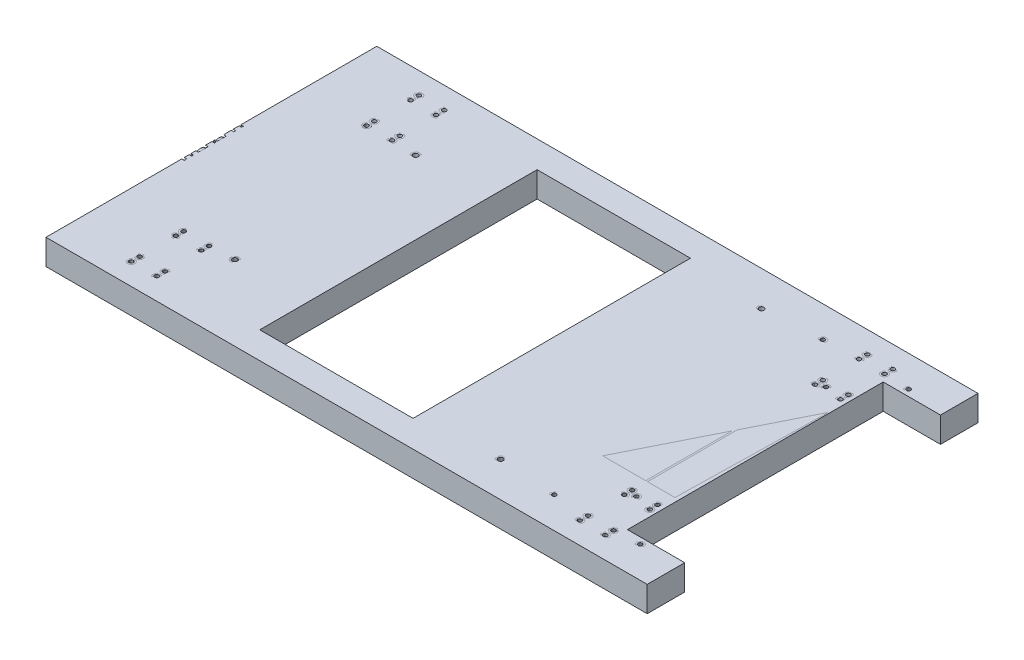
SolidWorks part; units mm, degrees
material "Magnesium Alloy"
ref_plane "Front Plane" through (0, 0, 0) normal (0, 0, 1) x (1, 0, 0)
ref_plane "Top Plane" through (0, 0, 0) normal (0, 1, 0) x (1, 0, 0)
ref_plane "Right Plane" through (0, 0, 0) normal (1, 0, 0) x (0, 0, -1)
sketch "Sketch1" plane through (0, 0, 0) normal (0, 1, 0) x (1, 0, 0)
  line L0 (0, 471.9498) -> (0, -504.9384) construction
  line L1 (-300.0375, 165.1) -> (300.0375, 165.1)
  line L2 (-300.0375, 165.1) -> (-300.0375, -165.1)
  line L3 (-300.0375, -165.1) -> (300.0375, -165.1)
  line L4 (300.0375, 165.1) -> (300.0375, -165.1)
  line L5 (-636.3607, 0) -> (748.0963, 0) construction
  dimension "D1" = 600.075
  dimension "D2" = 330.2
extrude "Boss-Extrude1" add sketch "Sketch1" along normal blind 25.4
sketch "Sketch2" plane through (-300.0375, 0, 0) normal (-1, 0, 0) x (0, 0, 1)
  line L0 (-165.1, 12.7) -> (165.1, 12.7) construction
  line L1 (-165.1, 25.4) -> (-165.1, 0) construction
  line L2 (165.1, 25.4) -> (165.1, 0) construction
  text T0 "Back" font "Century Gothic" height 19.05
extrude "Cut-Extrude1" cut sketch "Sketch2" against normal blind 2.54
sketch "Sketch3" plane through (300.0375, 0, 0) normal (1, 0, 0) x (0, 0, -1)
  line L0 (-165.1, 12.7) -> (165.1, 12.7) construction
  line L1 (-165.1, 25.4) -> (-165.1, 0) construction
  line L2 (165.1, 25.4) -> (165.1, 0) construction
  text T0 "Front" font "Century Gothic" height 19.05
extrude "Cut-Extrude2" cut sketch "Sketch3" against normal blind 2.54
sketch "Sketch4" plane through (0, 0, 0) normal (0, -1, 0) x (1, 0, 0)
  line L0 (407.1831, 0) -> (-551.8052, 0) construction
  line L1 (-113.3475, 138.43) -> (39.6875, 138.43)
  line L2 (-113.3475, 138.43) -> (-113.3475, -138.43)
  line L3 (-113.3475, -138.43) -> (39.6875, -138.43)
  line L4 (39.6875, 138.43) -> (39.6875, -138.43)
  line L5 (55, 0) -> (-55, 0) construction
  line L6 (-300.0375, -165.1) -> (-300.0375, 165.1) construction
  line L7 (300.0375, 165.1) -> (300.0375, -165.1) construction
  line L10 (-300.0375, 165.1) -> (300.0375, 165.1) construction
  dimension "D1" = 186.69
  dimension "D2" = 260.35
  dimension "D3" = 26.67
extrude "Cut-Extrude3" cut sketch "Sketch4" against normal up to next
ref_plane "Plane1" through (223.8375, 0, 0) normal (1, 0, 0) x (0, 0, -1)
ref_plane "Plane2" through (-223.8375, 0, 0) normal (-1, 0, 0) x (0, 0, 1)
sketch "Sketch7" plane through (0, 25.4, 0) normal (0, 1, 0) x (1, 0, 0)
  line L0 (-300.0375, -29.6562) -> (-300.0375, -165.1) construction
  line L1 (-300.0375, -165.1) -> (300.0375, -165.1) construction
  point P0 (-236.5375, -91.2978)
  point P1 (-236.5375, -135.2474)
  point P2 (-211.1375, -135.2474)
  point P3 (-211.1375, -91.2978)
  dimension "D1" = 63.5
  dimension "D2" = 63.5
  dimension "D3" = 88.9
  dimension "D4" = 88.9
  dimension "D5" = 29.8526
  dimension "D6" = 29.8526
  dimension "D7" = 43.9496
  dimension "D8" = 43.9496
hole_wizard "#21 (0.159) Diameter Hole1" positions "Sketch10" profile "Sketch11" hole size "#21" standard "ANSI Inch" end condition through all
sketch "Sketch10" plane through (0, 25.4, 0) normal (0, 1, 0) x (1, 0, 0)
  point P0 (-236.5375, -91.2978)
  point P3 (-211.1375, -91.2978)
  point P6 (-211.1375, -135.2474)
  point P9 (-236.5375, -135.2474)
sketch "Sketch11" plane through (-236.5375, 25.4, 91.2978) normal (1, 0, 0) x (0, 0, 1)
  line L0 (0, 0) -> (0, 25.4)
  line L1 (0, 25.4) -> (2.0193, 25.4)
  line L2 (2.0193, 25.4) -> (2.0193, 0)
  line L5 (2.0193, 0) -> (0, 0)
  line L11 (0, -6.35) -> (0, 107.95) construction
  dimension "Thru Hole Dia." = 4.0386
  dimension "Thru Hole Depth" = 25.4
mirror "Mirror3" about plane through (0, 0, 0) normal (1, 0, 0) of "#21 (0.159) Diameter Hole1"
mirror "Mirror4" about plane through (0, 0, 0) normal (0, 0, 1) of "Mirror3"
ref_axis "Axis1" through (-236.5375, 0, 91.2978) along (0, 1, 0)
ref_axis "Axis2" through (-211.1375, 0, 91.2978) along (0, 1, 0)
ref_axis "Axis3" through (-211.1375, 0, 135.2474) along (0, 1, 0)
ref_axis "Axis4" through (-236.5375, 0, 135.2474) along (0, 1, 0)
sketch "Sketch12" plane through (0, 25.4, 0) normal (0, 1, 0) x (1, 0, 0)
  point P0 (78.8458, -130.175)
ref_plane "Plane3" through (0, 0, 130.175) normal (0, 0, 1) x (1, 0, 0)
sketch "Sketch13" plane through (0, 0, 130.175) normal (0, 0, 1) x (1, 0, 0)
  line L0 (78.8458, 65.775) -> (78.8458, -43.461) construction
hole_wizard "Ø5.0mm Dowel Hole2" positions "Sketch16" profile "Sketch17" hole size "Ø5.0" standard "ANSI Metric" end condition through all
sketch "Sketch16" plane through (0, 25.4, 0) normal (0, 1, 0) x (1, 0, 0)
  circle A0 centre (118.8508, -130.175) radius 2.54
  circle A1 centre (118.8508, 130.175) radius 2.54
  circle A2 centre (-186.3725, 90.17) radius 2.54
  circle A3 centre (-186.3725, -90.17) radius 2.54
  point P3 (118.8508, -130.175)
  point P9 (118.8508, 130.175)
  point P12 (-186.3725, 90.17)
  point P21 (-186.3725, -90.17)
  point P24 (118.8508, -130.175)
sketch "Sketch17" plane through (118.8508, 25.4, 130.175) normal (1, 0, 0) x (0, 0, 1)
  line L0 (0, 0) -> (0, 25.4)
  line L1 (0, 25.4) -> (2.5, 25.4)
  line L2 (2.5, 25.4) -> (2.5, 0)
  line L5 (2.5, 0) -> (0, 0)
  line L11 (0, -6.35) -> (0, 107.95) construction
  dimension "Thru Hole Dia." = 5
  dimension "Thru Hole Depth" = 25.4
sketch "Sketch18" plane through (0, 25.4, 0) normal (0, 1, 0) x (1, 0, 0)
  line L0 (300.0375, 30.4067) -> (300.0375, 165.1) construction
  line L1 (300.0375, 127.635) -> (242.8875, 127.635)
  line L2 (300.0375, 127.635) -> (300.0375, -127.635)
  line L3 (300.0375, -127.635) -> (242.8875, -127.635)
  line L4 (242.8875, 127.635) -> (242.8875, -127.635)
  line L5 (300.0375, 165.1) -> (-300.0375, 165.1) construction
  line L6 (-300.0375, -165.1) -> (300.0375, -165.1) construction
  dimension "D1" = 37.465
  dimension "D2" = 37.465
  dimension "D3" = 57.15
extrude "Cut-Extrude4" cut sketch "Sketch18" against normal up to next
sketch "Sketch19" plane through (0, 12.7, 0) normal (0, -1, 0) x (-1, 0, 0)
  circle A0 centre (-218.7586, 94.615) radius 2.032
  circle A1 centre (-218.7586, 94.615) radius 2.032 construction
  circle A2 centre (-218.7586, -94.615) radius 2.032
  circle A3 centre (-218.7586, -94.615) radius 2.032 construction
  circle A4 centre (-176.2125, 133.985) radius 2.032
  circle A5 centre (-176.2125, 133.985) radius 2.032 construction
  circle A6 centre (-176.2125, -133.985) radius 2.032
  circle A7 centre (-176.2125, -133.985) radius 2.032 construction
extrude "Cut-Extrude5" cut sketch "Sketch19" along normal blind 12.7 and the other way blind 12.7
ref_axis "Axis5" through (176.2125, 0, -133.985) along (0, 1, 0)
ref_axis "Axis6" through (176.2125, 0, 133.985) along (0, 1, 0)
ref_axis "Axis7" through (218.7586, 0, -94.615) along (0, 1, 0)
ref_axis "Axis8" through (218.7586, 0, 94.615) along (0, 1, 0)
sketch "Sketch20" plane through (0, 25.4, 0) normal (0, 1, 0) x (1, 0, 0)
  line L0 (300.0375, 165.1) -> (-300.0375, 165.1) construction
  line L1 (300.0375, 127.635) -> (300.0375, 165.1) construction
  circle A0 centre (236.5375, 143.51) radius 2.0193
  dimension "D1" = 21.59
  dimension "D2" = 63.5
extrude "Cut-Extrude6" cut sketch "Sketch20" against normal up to next
sketch "Sketch21" plane through (0, 25.4, 0) normal (0, 1, 0) x (1, 0, 0)
  line L0 (300.0375, 165.1) -> (-300.0375, 165.1) construction
  line L1 (300.0375, 127.635) -> (300.0375, 165.1) construction
  circle A0 centre (211.1375, 143.51) radius 2.0193
  circle A1 centre (211.1375, 99.06) radius 2.0193
  circle A2 centre (236.5375, 99.06) radius 2.0193
  circle A3 centre (236.5375, 143.51) radius 2.0193 construction
  dimension "D1" = 21.59
  dimension "D2" = 25.4
  dimension "D3" = 4.0386
  dimension "D4" = 44.45
  dimension "D5" = 44.45
  dimension "D6" = 63.5
  dimension "D7" = 4.0386
  dimension "D8" = 25.4
  dimension "D9" = 4.0386
extrude "Cut-Extrude7" cut sketch "Sketch21" against normal up to next
pattern_linear "LPattern1" count 2 spacing 447.675 along (-1, 0, 0) of "Cut-Extrude7", "Cut-Extrude6"
mirror "Mirror5" about plane through (0, 0, 0) normal (0, 0, 1) of "LPattern1"
sketch "Sketch22" plane through (0, 25.4, 0) normal (0, 1, 0) x (1, 0, 0)
  line L0 (300.0375, -165.1) -> (300.0375, -127.635) construction
  line L1 (160.3375, -127.635) -> (300.0375, -127.635) construction
  circle A0 centre (261.9375, -133.985) radius 2.032
  dimension "D1" = 4.064
  dimension "D2" = 38.1
  dimension "D3" = 6.35
extrude "Cut-Extrude8" cut sketch "Sketch22" against normal up to next
mirror "Mirror6" about plane through (0, 0, 0) normal (0, 0, 1) of "Cut-Extrude8"
sketch "Sketch23" plane through (0, 25.4, 0) normal (0, 1, 0) x (1, 0, 0)
  circle A0 centre (-236.5375, 143.51) radius 2.0193
  circle A1 centre (-236.5375, 143.51) radius 3.6068
  circle A2 centre (-211.1375, 143.51) radius 2.0193
  circle A3 centre (-211.1375, 143.51) radius 3.6068
  circle A4 centre (-236.5375, 135.2474) radius 2.0193
  circle A5 centre (-236.5375, 135.2474) radius 3.6068
  circle A6 centre (-211.1375, 135.2474) radius 2.0193
  circle A7 centre (-211.1375, 135.2474) radius 3.6068
  circle A8 centre (-236.5375, 99.06) radius 2.0193
  circle A9 centre (-236.5375, 99.06) radius 3.6068
  circle A10 centre (-236.5375, 91.2978) radius 2.0193
  circle A11 centre (-236.5375, 91.2978) radius 3.6068
  circle A12 centre (-211.1375, 99.06) radius 2.0193
  circle A13 centre (-211.1375, 99.06) radius 3.6068
  circle A14 centre (-211.1375, 91.2978) radius 2.0193
  circle A15 centre (-211.1375, 91.2978) radius 3.6068
  circle A16 centre (-186.3725, 90.17) radius 2.5006
  circle A17 centre (-186.3725, 90.17) radius 4.0881
  circle A18 centre (118.8508, 130.175) radius 2.5006
  circle A19 centre (118.8508, 130.175) radius 4.0881
  circle A20 centre (176.2125, 133.985) radius 2.032
  circle A21 centre (211.1375, 99.06) radius 2.0193
  circle A22 centre (211.1375, 91.2978) radius 2.0193
  circle A23 centre (218.7586, 94.615) radius 2.032
  circle A24 centre (211.1375, 135.2474) radius 2.0193
  circle A25 centre (211.1375, 143.51) radius 2.0193
  circle A26 centre (236.5375, 143.51) radius 2.0193
  circle A27 centre (236.5375, 135.2474) radius 2.0193
  circle A28 centre (236.5375, 99.06) radius 2.0193
  circle A29 centre (236.5375, 91.2978) radius 2.0193
  circle A30 centre (261.9375, 133.985) radius 2.032
  circle A31 centre (176.2125, 133.985) radius 3.6195
  circle A32 centre (211.1375, 143.51) radius 3.6068
  circle A33 centre (211.1375, 135.2474) radius 3.6068
  circle A34 centre (211.1375, 99.06) radius 3.6068
  circle A35 centre (211.1375, 91.2978) radius 3.6068
  circle A36 centre (218.7586, 94.615) radius 3.6195
  circle A37 centre (236.5375, 91.2978) radius 3.6068
  circle A38 centre (236.5375, 99.06) radius 3.6068
  circle A39 centre (236.5375, 135.2474) radius 3.6068
  circle A40 centre (236.5375, 143.51) radius 3.6068
  circle A41 centre (261.9375, 133.985) radius 3.6195
  dimension "D1" = 1.5875
  dimension "D2" = 1.5875
  dimension "D3" = 1.5875
  dimension "D4" = 1.5875
  dimension "D5" = 1.5875
  dimension "D6" = 1.5875
  dimension "D7" = 1.5875
  dimension "D8" = 1.5875
  dimension "D9" = 1.5875
  dimension "D10" = 4.0386
  dimension "D11" = 4.0386
  dimension "D12" = 4.0386
  dimension "D13" = 4.0386
  dimension "D14" = 5.0013
  dimension "D15" = 4.0386
  dimension "D16" = 4.0386
  dimension "D17" = 4.0386
  dimension "D18" = 4.0386
  dimension "D19" = 1.5875
  dimension "D20" = 4.064
  dimension "D21" = 1.5875
  dimension "D22" = 1.5875
  dimension "D23" = 1.5875
  dimension "D24" = 1.5875
  dimension "D25" = 1.5875
  dimension "D26" = 1.5875
  dimension "D27" = 1.5875
  dimension "D28" = 1.5875
  dimension "D29" = 1.5875
  dimension "D30" = 1.5875
  dimension "D31" = 1.5875
  dimension "D32" = 5.0013
  dimension "D33" = 4.0386
  dimension "D34" = 4.0386
  dimension "D35" = 4.064
  dimension "D36" = 4.0386
  dimension "D37" = 4.0386
  dimension "D38" = 4.0386
  dimension "D39" = 4.0386
  dimension "D40" = 4.0386
  dimension "D41" = 4.0386
  dimension "D42" = 4.064
extrude "Boss-Extrude2" add sketch "Sketch23" against normal blind 26.67 separate body
mirror "Mirror9" about plane through (0, 0, 0) normal (0, 0, 1) of bodies 128 130 127 131 125 123 124 126 136 137 139 140 142 141 143 134 135 133 132 138 129
sketch "Sketch24" plane through (0, 25.4, 0) normal (0, 1, 0) x (1, 0, 0)
  line L0 (242.8875, 127.635) -> (242.8875, -127.635) construction
  line L1 (242.8875, 76.2) -> (166.6875, 76.2)
  line L2 (242.8875, 76.2) -> (242.8875, -76.2)
  line L3 (242.8875, -76.2) -> (166.6875, -76.2)
  line L4 (166.6875, 76.2) -> (166.6875, -76.2)
  line L5 (-300.0375, -165.1) -> (300.0375, -165.1) construction
  line L6 (300.0375, 165.1) -> (-300.0375, 165.1) construction
  dimension "D1" = 88.9
  dimension "D2" = 88.9
  dimension "D3" = 76.2
extrude "Boss-Extrude3" add sketch "Sketch24" against normal blind 25.4 separate body
